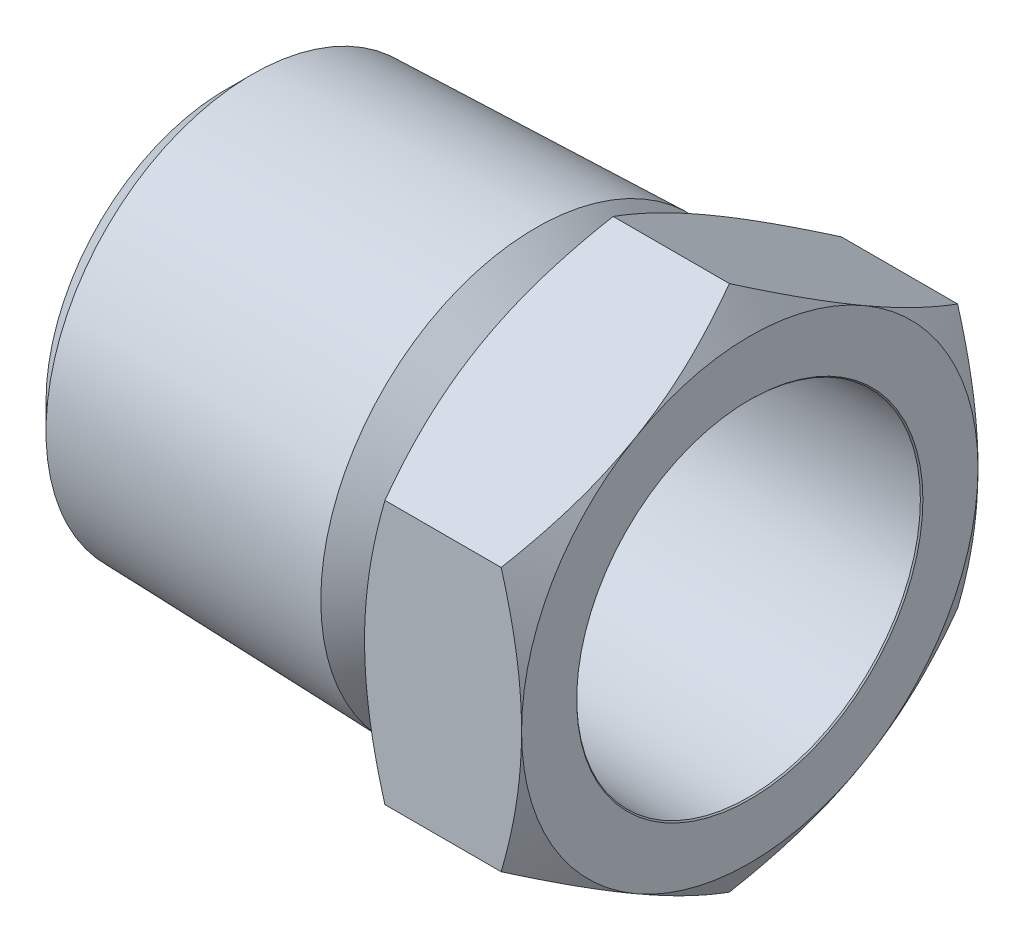
SolidWorks part; units mm, degrees
ref_plane "Front" through (0, 0, 0) normal (0, 0, 1) x (1, 0, 0)
ref_plane "Top" through (0, 0, 0) normal (0, 1, 0) x (1, 0, 0)
ref_plane "Right" through (0, 0, 0) normal (1, 0, 0) x (0, 0, -1)
sketch "Sketch1" plane through (0, 0, 0) normal (0, 0, 1) x (1, 0, 0)
  line L0 (-10.922, 0) -> (10.922, 0) construction
  dimension "L" = 21.844
ref_plane "Plane1" through (-10.922, 0, 0) normal (1, 0, 0) x (0, 0, -1)
sketch "Sketch2" plane through (-10.922, 0, 0) normal (1, 0, 0) x (0, 0, -1)
  circle A0 centre (0, 0) radius 8.5725
  dimension "OD" = 17.145
extrude "Extrude1" add sketch "Sketch2" along normal up to vertex (21.844 mm away) draft 1.783 up to point (10.922, 0, 0) draft outward yes
sketch "Sketch3" plane through (-10.922, 0, 0) normal (-1, 0, 0) x (0, 0, 1)
  circle A1 centre (0, 0) radius 8.5725
  circle A2 centre (0, 0) radius 8.5725
  dimension "D1" = 0
curve "Helix/Spiral1" parameters "pitch"=1.4111
sketch "Sketch4" plane through (0, 0, 0) normal (0, 0, 1) x (1, 0, 0)
  line L0 (-12.1567, 8.5725) -> (-11.6276, 7.656)
  line L1 (-11.6276, 7.656) -> (-11.4512, 7.656)
  line L2 (-11.4512, 7.656) -> (-10.922, 8.5725)
  line L3 (-12.1567, 8.5725) -> (-10.922, 8.5725) construction
  line L4 (-11.8921, 8.1142) -> (-11.1866, 8.1142) construction
  line L5 (-11.5394, 7.656) -> (-11.5394, 8.5725) construction
  line L6 (-12.1567, 8.5725) -> (-10.7821, 8.8149)
  line L7 (-10.922, 8.5725) -> (-10.7821, 8.8149)
  line L8 (-10.922, 8.5725) -> (-10.922, -8.5725) construction
  dimension "D1" = 10
  dimension "D2" = 0.1764
  dimension "D3" = 0.7056
  dimension "D4" = 60
sweep "Cut-Sweep1" [suppressed] cut profiles "Sketch4" path "Helix/Spiral1"
sketch "Sketch5" plane through (-10.922, 0, 0) normal (1, 0, 0) x (0, 0, -1)
  circle A0 centre (0, 0) radius 7.656 construction
  circle A1 centre (0, 0) radius 7.529
  dimension "D1" = 0.127
extrude "Cut-Extrude1" cut sketch "Sketch5" along normal through all draft 45 flip side to cut
ref_plane "Plane2" through (10.922, 0, 0) normal (1, 0, 0) x (0, 0, -1)
ref_plane "Plane3" through (4.3688, 0, 0) normal (1, 0, 0) x (0, 0, -1)
sketch "Sketch8" plane through (4.3688, 0, 0) normal (1, 0, 0) x (0, 0, -1)
  circle A2 centre (0, 0) radius 14.9225
  circle A3 centre (0, 0) radius 14.9225
  dimension "D1" = 6.35
extrude "Cut-Extrude4" cut sketch "Sketch8" along normal through all
sketch "Sketch9" plane through (4.3688, 0, 0) normal (1, 0, 0) x (0, 0, -1)
  circle A0 centre (0, 0) radius 8.5725 construction
  circle A2 centre (0, 0) radius 7.656
extrude "Cut-Extrude5" cut sketch "Sketch9" against normal blind 1.0583 flip side to cut
ref_plane "Plane4" through (3.3105, 0, 0) normal (1, 0, 0) x (0, 0, -1)
sketch "Sketch10" plane through (3.3105, 0, 0) normal (1, 0, 0) x (0, 0, -1)
  circle A1 centre (0, 0) radius 7.656
  circle A2 centre (0, 0) radius 7.656
  dimension "D1" = 0
extrude "Cut-Extrude6" cut sketch "Sketch10" against normal through all draft 45 flip side to cut
sketch "Sketch6" plane through (10.922, 0, 0) normal (1, 0, 0) x (0, 0, -1)
  line L1 (0, 10.9985) -> (-9.525, 5.4993)
  line L2 (-9.525, 5.4993) -> (-9.525, -5.4993)
  line L3 (-9.525, -5.4993) -> (0, -10.9985)
  line L4 (0, -10.9985) -> (9.525, -5.4993)
  line L5 (9.525, -5.4993) -> (9.525, 5.4993)
  line L6 (9.525, 5.4993) -> (0, 10.9985)
  circle A0 centre (0, 0) radius 9.525 construction
  dimension "Hex" = 19.05
extrude "Extrude2" add sketch "Sketch6" against normal blind 6.5532
sketch "Sketch7" plane through (10.922, 0, 0) normal (1, 0, 0) x (0, 0, -1)
  line L0 (0, 10.9985) -> (-9.525, 5.4993) construction
  circle A0 centre (0, 0) radius 9.525
extrude "Cut-Extrude2" cut sketch "Sketch7" against normal through all draft 60 flip side to cut
sketch "Sketch18" plane through (4.3688, 0, 0) normal (-1, 0, 0) x (0, 0, 1)
  circle A0 centre (0, 0) radius 9.525 construction
  circle A1 centre (0, 0) radius 9.525
extrude "Extrude3" cut sketch "Sketch18" against normal blind 10 draft 60 flip side to cut
ref_plane "Plane5" through (0.762, 0, 0) normal (1, 0, 0) x (0, 0, -1)
sketch "Sketch11" plane through (0.762, 0, 0) normal (1, 0, 0) x (0, 0, -1)
  circle A0 centre (0, 0) radius 6.858
  dimension "OD2" = 13.716
extrude "Cut-Extrude7" cut sketch "Sketch11" along normal through all draft 1.783 draft outward yes
sketch "Sketch12" plane through (0.762, 0, 0) normal (1, 0, 0) x (0, 0, -1)
  circle A0 centre (0, 0) radius 6.858 construction
  circle A1 centre (0, 0) radius 6.858
curve "Helix/Spiral2" parameters "pitch 2"=1.4111
sketch "Sketch16" plane through (10.922, 0, 0) normal (1, 0, 0) x (0, 0, -1)
  circle A2 centre (0, 0) radius 7.2251
  circle A3 centre (0, 0) radius 7.2251
  dimension "D1" = 0.0508
sketch "Sketch14" plane through (0, 0, 0) normal (0, 0, 1) x (1, 0, 0)
  line L0 (-0.4727, 6.858) -> (0.762, 6.858) construction
  line L1 (0.762, 6.858) -> (0.2328, 5.9415) construction
  line L2 (0.2328, 5.9415) -> (0.0564, 5.9415)
  line L3 (0.0564, 5.9415) -> (-0.4727, 6.858)
  line L4 (-0.2081, 6.3997) -> (0.4974, 6.3997) construction
  line L5 (0.1446, 5.9415) -> (0.1446, 6.858) construction
  line L6 (-0.4727, 6.858) -> (0.9019, 7.1004)
  line L7 (0.9019, 7.1004) -> (0.2328, 5.9415)
  line L8 (0.762, -6.858) -> (0.762, 6.858) construction
  dimension "D1" = 10
  dimension "D2" = 60
  dimension "D3" = 0.1764
  dimension "D4" = 0.7056
sweep "Sweep1" [suppressed] add profiles "Sketch14" path "Helix/Spiral2"
sketch "Sketch15" plane through (10.922, 0, 0) normal (1, 0, 0) x (0, 0, -1)
  line L6 (0, 10.9985) -> (-9.525, 5.4993)
  line L7 (-9.525, 5.4993) -> (-9.525, -5.4993)
  line L8 (-9.525, -5.4993) -> (0, -10.9985)
  line L9 (0, -10.9985) -> (9.525, -5.4993)
  line L10 (9.525, -5.4993) -> (9.525, 5.4993)
  line L11 (9.525, 5.4993) -> (0, 10.9985)
  line L12 (0, 10.9985) -> (-9.525, 5.4993)
  line L13 (-9.525, 5.4993) -> (-9.525, -5.4993)
  line L14 (-9.525, -5.4993) -> (0, -10.9985)
  line L15 (0, -10.9985) -> (9.525, -5.4993)
  line L16 (9.525, -5.4993) -> (9.525, 5.4993)
  line L17 (9.525, 5.4993) -> (0, 10.9985)
  dimension "D1" = 0
extrude "Cut-Extrude8" [suppressed] cut sketch "Sketch15" along normal through all
extrude "Cut-Extrude9" cut sketch "Sketch16" against normal blind 6.35 draft 45
sketch "Sketch17" plane through (0, 0, 0) normal (0, 0, 1) x (1, 0, 0)
  line L1 (-10.922, 6.3997) -> (0.762, 6.3997)
  line L2 (0.762, 6.3997) -> (0.762, 0)
  line L3 (0.762, 0) -> (-10.922, 0)
  line L4 (-10.922, 0) -> (-10.922, 6.3997)
  line L5 (-10.922, -8.5725) -> (-10.922, 8.5725) construction
  line L6 (0.762, -6.858) -> (0.762, 6.858) construction
revolve "Cut-Revolve1" cut sketch "Sketch17" angle 360 about L0
equation "\"D3@Helix/Spiral1\" = \"L@Sketch1\""
equation "\"D2@Sketch4\" = \"pitch@Helix/Spiral1\"*.125"
equation "\"D3@Sketch4\" = \"pitch@Helix/Spiral1\"*.5"
equation "\"D1@Extrude2\" = \"L@Sketch1\"*.3"
equation "\"D1@Plane3\" = \"D1@Extrude2\""
equation "\"D1@Cut-Extrude5\" = \"pitch@Helix/Spiral1\"*.75"
equation "\"D1@Plane4\" = \"D1@Cut-Extrude5\""
equation "\"D3@Helix/Spiral2\" = \"thread engagement @Plane5\"+.250"
equation "\"D3@Sketch14\" = \"pitch 2@Helix/Spiral2\"*.125"
equation "\"D4@Sketch14\" = \"pitch 2@Helix/Spiral2\"*.50"
